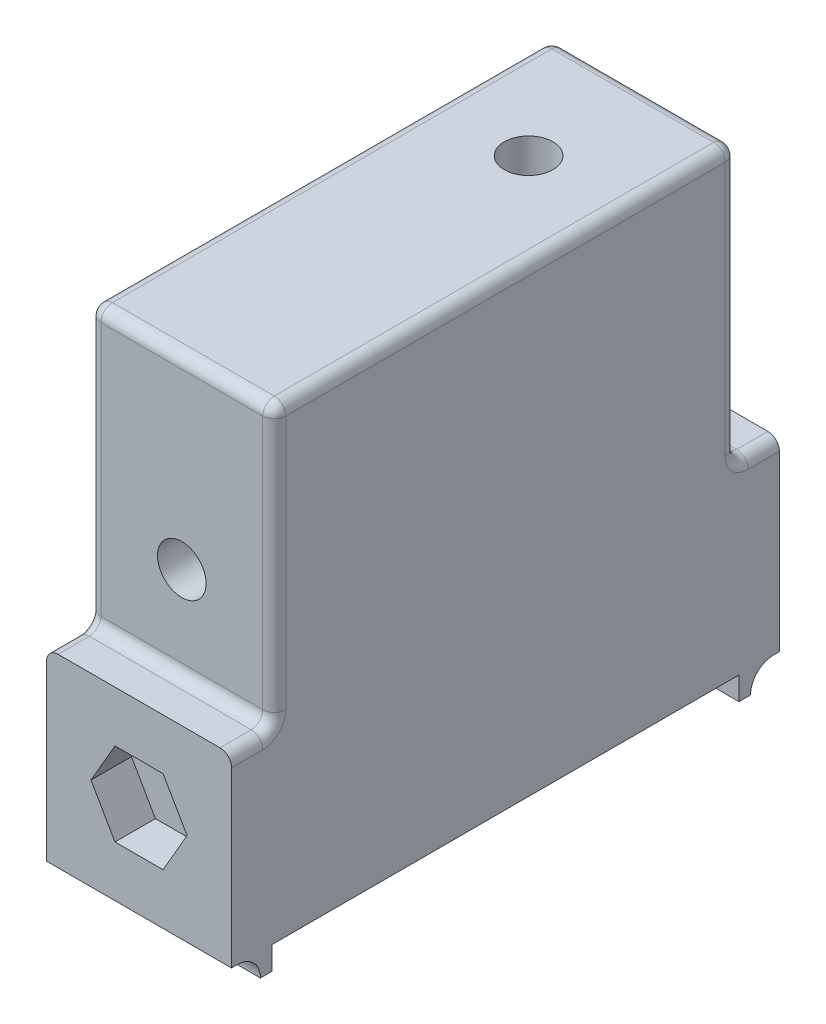
SolidWorks part; units mm, degrees
ref_plane "Front Plane" through (0, 0, 0) normal (0, 0, 1) x (1, 0, 0)
ref_plane "Top Plane" through (0, 0, 0) normal (0, 1, 0) x (1, 0, 0)
ref_plane "Right Plane" through (0, 0, 0) normal (1, 0, 0) x (0, 0, -1)
sketch "Sketch1" plane through (0, 0, 0) normal (0, 1, 0) x (1, 0, 0)
  line L1 (-8, 20) -> (8, 20)
  line L2 (-8, 20) -> (-8, -20)
  line L3 (-8, -20) -> (8, -20)
  line L4 (8, 20) -> (8, -20)
  line L5 (-8, 20) -> (8, -20) construction
  line L6 (-8, -20) -> (8, 20) construction
  point P4 (0, 0)
  dimension "D1" = 40
  dimension "D2" = 16
extrude "Boss-Extrude1" add sketch "Sketch1" along normal blind 40
sketch "Sketch2" plane through (0, 0, 0) normal (0, -1, 0) x (1, 0, 0)
  line L1 (-8, 23.7) -> (8, 23.7)
  line L2 (-8, 23.7) -> (-8, 20)
  line L3 (-8, 20) -> (8, 20)
  line L4 (8, 23.7) -> (8, 20)
  line L5 (-8, 23.7) -> (8, 20) construction
  line L6 (-8, 20) -> (8, 23.7) construction
  line L7 (-8, -20) -> (8, -20)
  line L8 (-8, -20) -> (-8, -23.7)
  line L9 (-8, -23.7) -> (8, -23.7)
  line L10 (8, -20) -> (8, -23.7)
  line L11 (-8, -20) -> (8, -23.7) construction
  line L12 (-8, -23.7) -> (8, -20) construction
  point P4 (0, 21.85)
  point P12 (0, -21.85)
  dimension "D1" = 3.7
  dimension "D2" = 3.7
extrude "Boss-Extrude2" add sketch "Sketch2" against normal blind 16
sketch "Sketch3" plane through (0, 0, -23.7) normal (0, 0, -1) x (-1, 0, 0)
  line L0 (-8, 16) -> (8, 0) construction
  line L1 (8, 16) -> (-8, 0) construction
  line L3 (2.0785, 11.6) -> (-2.0785, 11.6)
  line L4 (-2.0785, 11.6) -> (-4.1569, 8)
  line L5 (-4.1569, 8) -> (-2.0785, 4.4)
  line L6 (-2.0785, 4.4) -> (2.0785, 4.4)
  line L7 (2.0785, 4.4) -> (4.1569, 8)
  line L8 (4.1569, 8) -> (2.0785, 11.6)
  circle A1 centre (0, 8) radius 3.6 construction
  dimension "D1" = 7.2
sketch "Sketch5" plane through (0, 0, 0) normal (0, -1, 0) x (1, 0, 0)
  line L0 (-8, -23.7) -> (-8, 23.7) construction
  line L1 (-5, 17) -> (5, 17)
  line L2 (-5, 17) -> (-5, -17)
  line L3 (-5, -17) -> (5, -17)
  line L4 (5, 17) -> (5, -17)
  line L5 (-5, 17) -> (5, -17) construction
  line L6 (-5, -17) -> (5, 17) construction
  line L8 (8, -20) -> (-8, -20) construction
  line L9 (8, -20) -> (-8, -20) construction
  point P4 (0, 0)
  dimension "D1" = 3
  dimension "D2" = 3
extrude "Cut-Extrude3" cut sketch "Sketch5" against normal blind 37
fillet "Fillet1" radius 1 14 edges at (0, 16, 20) (0, 16, -20) (8, 16, 21.85) (8, 28, 20) (8, 28, -20) (8, 16, -21.85) (-8, 16, -21.85) (-8, 28, -20) (-8, 28, 20) (-8, 16, 21.85) (0, 40, -20) (8, 40, 0) (0, 40, 20) (-8, 40, 0)
fillet "Fillet2" radius 1 8 edges at (0, 37, 17) (5, 37, 0) (0, 37, -17) (-5, 37, 0) (-5, 18.5, -17) (5, 18.5, -17) (-5, 18.5, 17) (5, 18.5, 17)
sketch "Sketch8" plane through (0, 0, 0) normal (0, -1, 0) x (1, 0, 0)
  line L0 (-8, 20) -> (8, 20) construction
  line L1 (-8, 20) -> (8, 20) construction
  line L2 (0, 0) -> (0, 20) construction
  line L8 (-8, -23.7) -> (8, -23.7)
  line L13 (8, -23.7) -> (8, 23.7)
  line L14 (8, 23.7) -> (-8, 23.7)
  line L15 (-8, 23.7) -> (-8, -23.7)
  line L16 (-8, -23.7) -> (8, -23.7)
  line L21 (8, -23.7) -> (8, 23.7)
  line L22 (8, 23.7) -> (-8, 23.7)
  line L23 (-8, 23.7) -> (-8, -23.7)
  circle A0 centre (0, 0) radius 20 construction
  dimension "D2" = 20
  dimension "D1" = 0
extrude "Cut-Extrude6" cut sketch "Sketch3" against normal blind 3.5
sketch "Measure Shearing Area" plane through (0, 0, -23.7) normal (0, 0, -1) x (-1, 0, 0)
  line L0 (-4.1569, 8) -> (-4.1569, 0)
  line L1 (8, 0) -> (-8, 0) construction
  line L2 (-4.1569, 0) -> (4.1569, 0)
  line L3 (4.1569, 0) -> (4.1569, 8)
  line L4 (4.1569, 8) -> (2.0785, 4.4)
  line L5 (2.0785, 4.4) -> (-2.0785, 4.4)
  line L6 (-2.0785, 4.4) -> (-4.1569, 8)
mirror "Mirror2" about plane through (0, 0, 0) normal (0, 0, 1) of "Cut-Extrude6"
sketch "Sketch9" plane through (0, 0, 0) normal (0, -1, 0) x (1, 0, 0)
  line L0 (-8, -23.7) -> (-8, 23.7) construction
  line L1 (-8, 21.2) -> (8, 21.2)
  line L2 (-8, 21.2) -> (-8, 20.2)
  line L3 (-8, 20.2) -> (8, 20.2)
  line L4 (8, 21.2) -> (8, 20.2)
  line L5 (-8, 21.2) -> (8, 20.2) construction
  line L6 (-8, 20.2) -> (8, 21.2) construction
  line L7 (8, 23.7) -> (8, -23.7) construction
  line L8 (-8, 0) -> (8, 0) construction
  line L9 (-8, -20.2) -> (8, -20.2)
  line L10 (8, -21.2) -> (8, -20.2)
  line L11 (-8, -21.2) -> (8, -21.2)
  line L12 (-8, -21.2) -> (-8, -20.2)
  point P4 (0, 20.7)
  dimension "D1" = 20.2
  dimension "D2" = 1
extrude "Boss-Extrude3" add sketch "Sketch9" along normal blind 2
sketch "Sketch12" plane through (0, 0, 20) normal (0, 0, 1) x (1, 0, 0)
  line L0 (-8, 28) -> (8, 28) construction
  line L1 (0, 0) -> (0, 40) construction
  line L2 (-7, 40) -> (7, 40) construction
  line L3 (-8, 17) -> (-8, 39) construction
  line L4 (8, 39) -> (8, 17) construction
  line L6 (-7, 21.9) -> (7, 21.9) construction
  line L7 (-7, 39) -> (-7, 17) construction
  line L8 (7, 17) -> (7, 39) construction
  line L9 (7, 16) -> (-7, 16) construction
  circle A1 centre (0, 24) radius 2.1
  dimension "D1" = 4.2
  dimension "D2" = 4
  dimension "D3" = 5.9
sketch "Sketch13" plane through (0, 40, 0) normal (0, 1, 0) x (1, 0, 0)
  line L0 (-8, 0) -> (8, 0) construction
  line L1 (0, 23.7) -> (0, -23.7) construction
  line L2 (8, 19) -> (8, -19) construction
  line L3 (-8, -19) -> (-8, 19) construction
  line L4 (-7, 23.7) -> (7, 23.7) construction
  line L5 (7, -23.7) -> (-7, -23.7) construction
  circle A1 centre (0, 10) radius 2.1
  dimension "D1" = 4.2
  dimension "D2" = 10
extrude "Cut-Extrude7" cut sketch "Sketch12" against normal up to next
extrude "Cut-Extrude8" cut sketch "Sketch13" against normal up to next
fillet "Fillet3" radius 2 2 edges at (0, 0, 21.2) (0, 0, -21.2)
